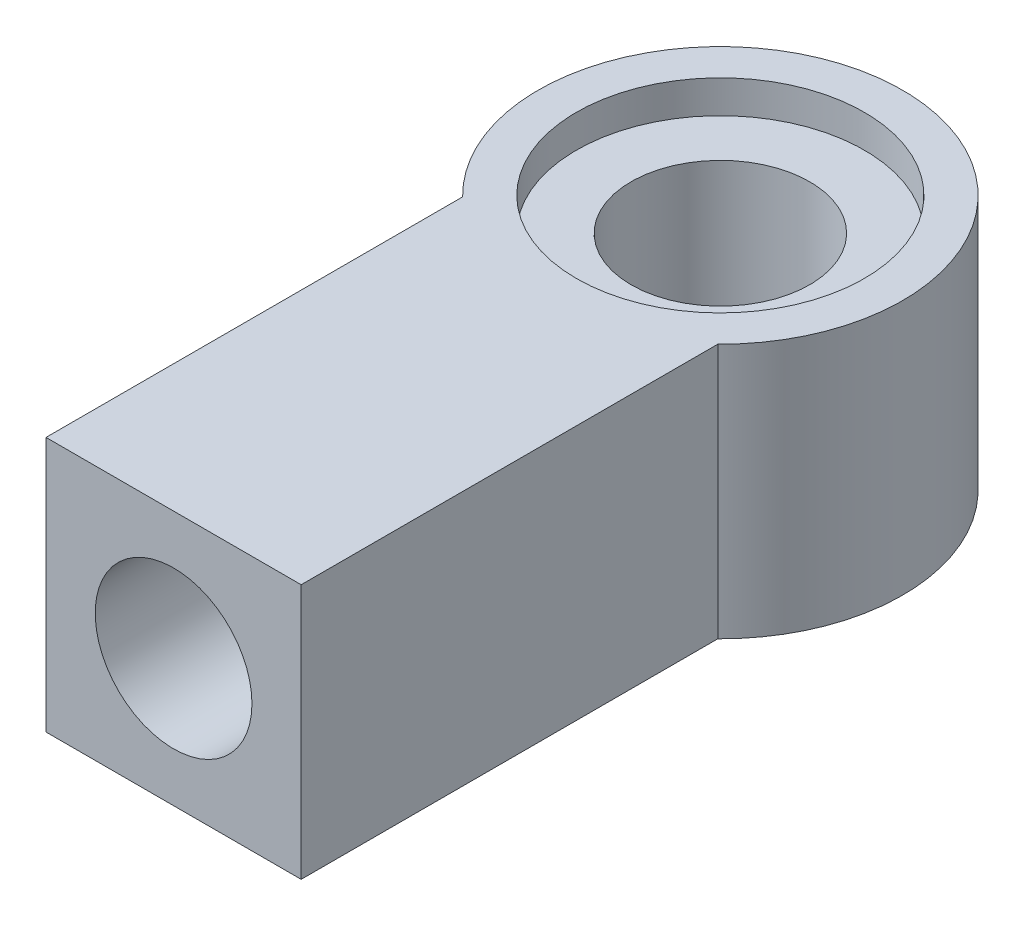
SolidWorks part; units mm, degrees
ref_plane "Front Plane" through (0, 0, 0) normal (0, 0, 1) x (1, 0, 0)
ref_plane "Top Plane" through (0, 0, 0) normal (0, 1, 0) x (1, 0, 0)
ref_plane "Right Plane" through (0, 0, 0) normal (1, 0, 0) x (0, 0, -1)
sketch "Sketch1" plane through (0, 0, 0) normal (0, 1, 0) x (1, 0, 0)
  circle A0 centre (0, 0) radius 5
  circle A1 centre (0, 0) radius 2.45
  dimension "D1" = 10
  dimension "D2" = 4.9
extrude "Boss-Extrude1" add sketch "Sketch1" along normal blind 7
ref_plane "Plane1" through (0, 0, 5) normal (0, 0, 1) x (1, 0, 0)
sketch "Sketch2" plane through (0, 0, 5) normal (0, 0, 1) x (1, 0, 0)
  line L0 (5, 7) -> (-5, 7) construction
  line L1 (3.5, 7) -> (-3.5, 7)
  line L2 (0, 7) -> (0, 0)
  line L3 (3.5, 0) -> (-3.5, 0)
  line L4 (-3.5, 7) -> (-3.5, 0)
  line L5 (-5, 0) -> (5, 0) construction
  line L6 (3.5, 7) -> (3.5, 0)
  dimension "D1" = 3.5
extrude "Boss-Extrude3" add sketch "Sketch2" against normal blind 1.5 contours L1 L4 L3 L2 | L6 L1 L2 L3 region at (1.75, 3.5, 5) region at (-1.75, 3.5, 5)
sketch "Sketch4" plane through (0, 0, 5) normal (0, 0, 1) x (1, 0, 0)
  line L1 (-3.5, 7) -> (3.5, 7)
  line L2 (-3.5, 7) -> (-3.5, 0)
  line L3 (-3.5, 0) -> (3.5, 0)
  line L4 (3.5, 7) -> (3.5, 0)
  circle A0 centre (0, 3.5) radius 2.15
  dimension "D1" = 4.3
extrude "Boss-Extrude4" add sketch "Sketch4" along normal blind 10
sketch "Sketch5" plane through (0, 7, 0) normal (0, 1, 0) x (1, 0, 0)
  circle A0 centre (0, 0) radius 3.95
  dimension "D1" = 7.9
extrude "Cut-Extrude1" cut sketch "Sketch5" against normal blind 0.9
